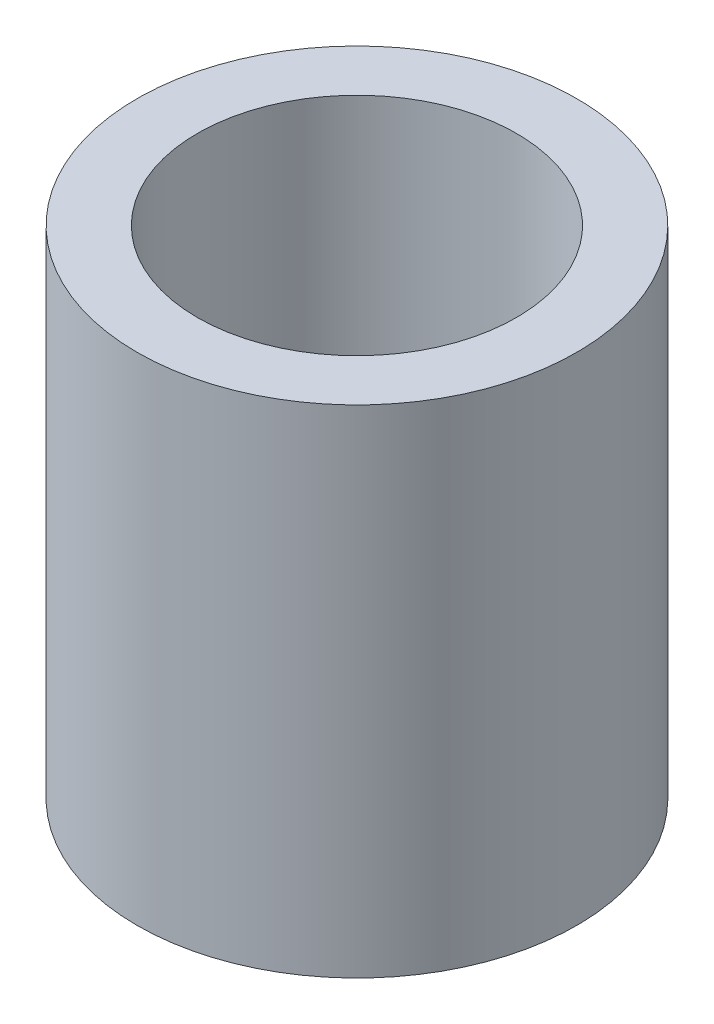
SolidWorks part; units mm, degrees
ref_plane "Front Plane" through (0, 0, 0) normal (0, 0, 1) x (1, 0, 0)
ref_plane "Top Plane" through (0, 0, 0) normal (0, 1, 0) x (1, 0, 0)
ref_plane "Right Plane" through (0, 0, 0) normal (1, 0, 0) x (0, 0, -1)
sketch "Sketch1" plane through (0, 0, 0) normal (0, 1, 0) x (1, 0, 0)
  circle A0 centre (0, 0) radius 3.1
  dimension "D1" = 6.2
extrude "Boss-Extrude1" add sketch "Sketch1" along normal blind 7
sketch "Sketch2" plane through (0, 7, 0) normal (0, 1, 0) x (1, 0, 0)
  circle A0 centre (0, 0) radius 2.25
  dimension "D1" = 4.5
extrude "Cut-Extrude1" cut sketch "Sketch2" against normal blind 7
